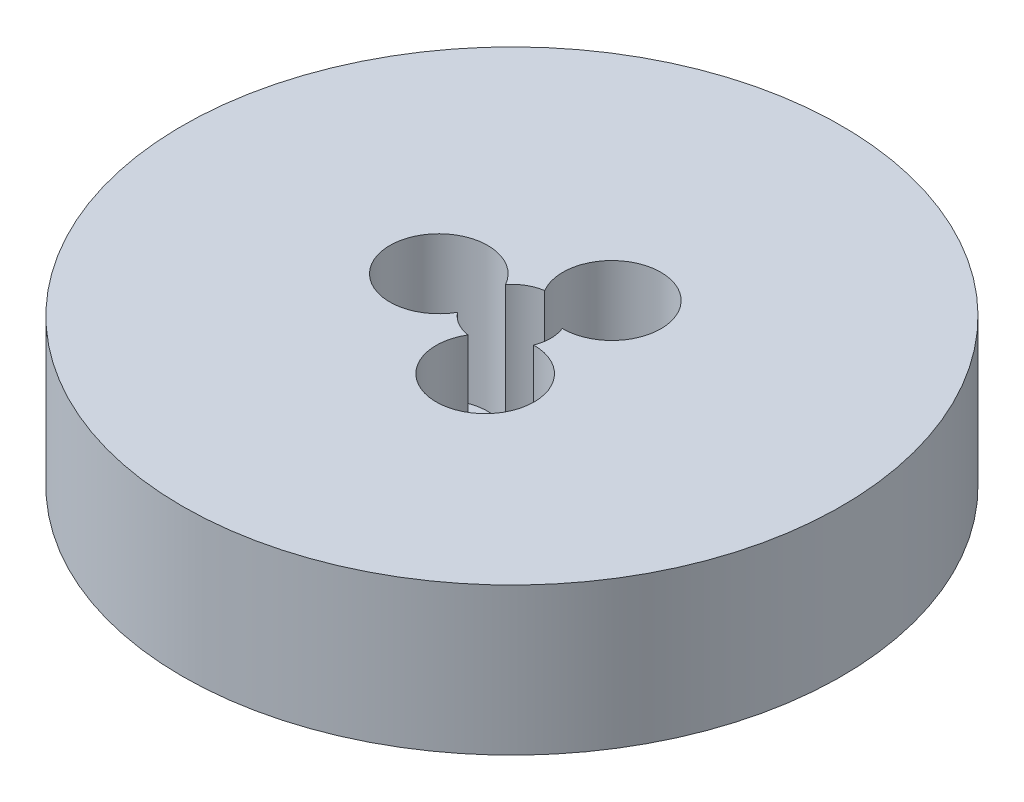
SolidWorks part; units mm, degrees
ref_plane "Front Plane" through (0, 0, 0) normal (0, 0, 1) x (1, 0, 0)
ref_plane "Top Plane" through (0, 0, 0) normal (0, 1, 0) x (1, 0, 0)
ref_plane "Right Plane" through (0, 0, 0) normal (1, 0, 0) x (0, 0, -1)
sketch "Sketch1" plane through (0, 0, 0) normal (0, 1, 0) x (1, 0, 0)
  circle A0 centre (0, 0) radius 42.5
  dimension "FLANGE_OD" = 85
extrude "Boss-Extrude1" add sketch "Sketch1" along normal blind 19
sketch "Sketch2" plane through (0, 0, 0) normal (0, 1, 0) x (1, 0, 0)
  circle A0 centre (0, 0) radius 5
  dimension "BORE_D" = 10
extrude "Cut-Extrude1" cut sketch "Sketch2" along normal through all
sketch "Sketch3" plane through (0, 19, 0) normal (0, 1, 0) x (1, 0, 0)
  circle A0 centre (0, 0) radius 9.4321 construction
  circle A1 centre (-9.4321, 0) radius 6.3219
  dimension "BOLT_D" = 12.6438
  dimension "BOLT_PCD" = 18.8641
extrude "Cut-Extrude2" cut sketch "Sketch3" against normal blind 18.5266
pattern_circular "CirPattern1" count 3 over 360 about axis through (0, 0, 0) along (0, 1, 0) of "Cut-Extrude2"
